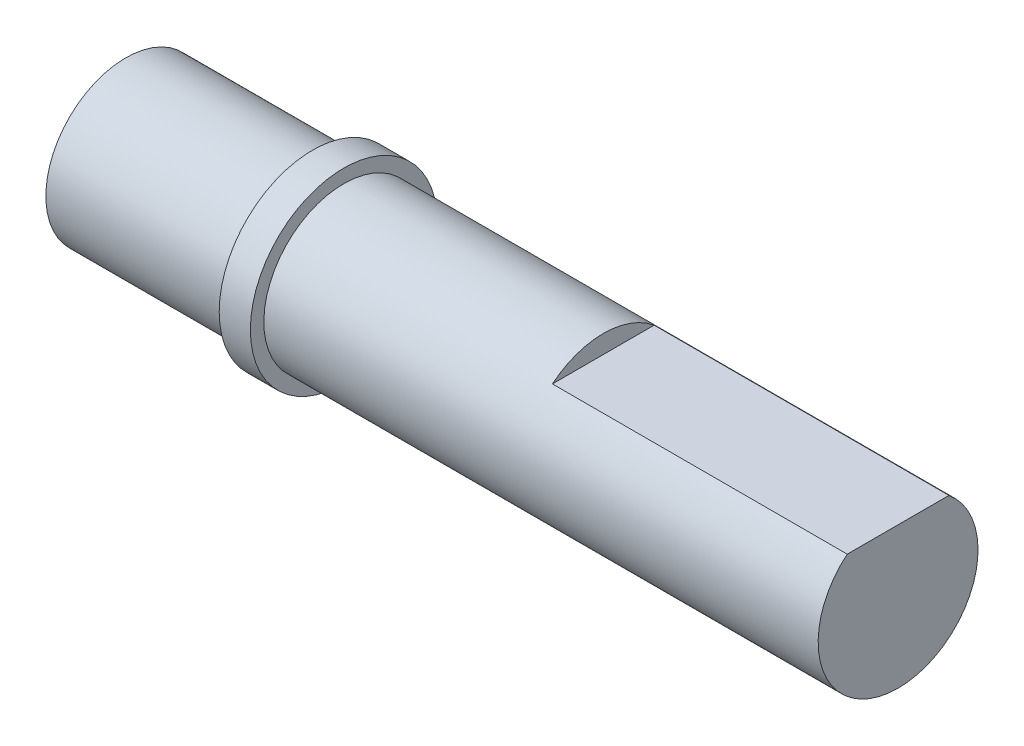
SolidWorks part; units mm, degrees
ref_plane "Front Plane" through (0, 0, 0) normal (0, 0, 1) x (1, 0, 0)
ref_plane "Top Plane" through (0, 0, 0) normal (0, 1, 0) x (1, 0, 0)
ref_plane "Right Plane" through (0, 0, 0) normal (1, 0, 0) x (0, 0, -1)
sketch "Sketch9" plane through (0, 0, 0) normal (1, 0, 0) x (0, 0, -1)
  line L0 (-2.45, 2.9698) -> (2.45, 2.9698)
  circle A0 centre (0, 0) radius 4.5
  circle A1 centre (0, 0) radius 3.85
  dimension "D1" = 4.9
  dimension "D2" = 7.7
  dimension "D3" = 9
extrude "Boss-Extrude1" add sketch "Sketch9" along normal blind 28.2 contours L0 A1 region at (0, -0.2248, 0)
extrude "Boss-Extrude2" add sketch "Sketch9<6>" along normal blind 1.5 contours A0 A1 region at (0, 0, 4.3727)
sketch "Sketch9<6>" plane through (0, 0, 0) normal (1, 0, 0) x (0, 0, -1) same geometry as "Sketch9"
extrude "Boss-Extrude3" add sketch "Sketch9<7>" along normal blind 14 contours L0 A1 region at (0, 3.3256, 0)
sketch "Sketch9<7>" plane through (0, 0, 0) normal (1, 0, 0) x (0, 0, -1) same geometry as "Sketch9"
extrude "Boss-Extrude4" add sketch "Sketch9<8>" against normal blind 9 contours L0 A1 | L0 A1 region at (0, 3.3256, 0) region at (0, -0.2248, 0)
sketch "Sketch9<8>" plane through (0, 0, 0) normal (1, 0, 0) x (0, 0, -1) same geometry as "Sketch9"
